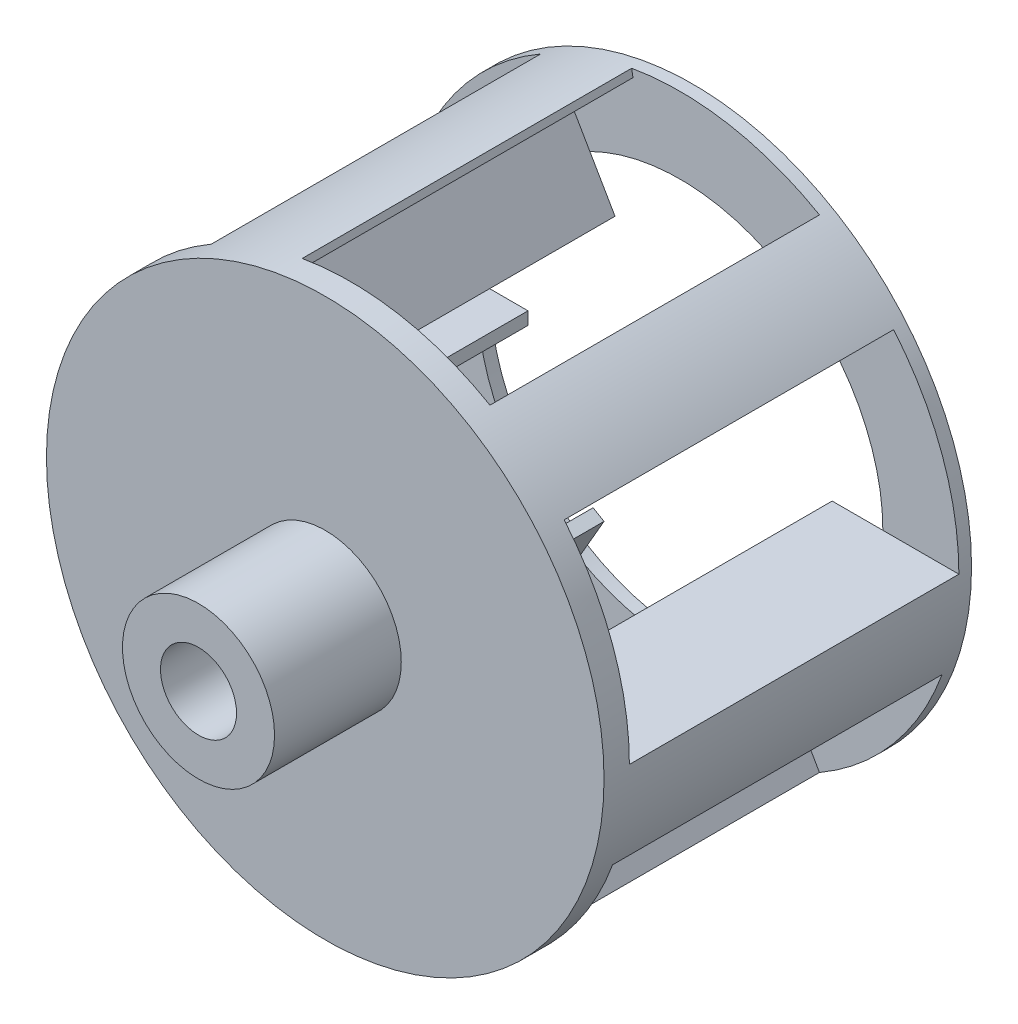
SolidWorks part; units mm, degrees
ref_plane "Front Plane" through (0, 0, 0) normal (0, 0, 1) x (1, 0, 0)
ref_plane "Top Plane" through (0, 0, 0) normal (0, 1, 0) x (1, 0, 0)
ref_plane "Right Plane" through (0, 0, 0) normal (1, 0, 0) x (0, 0, -1)
sketch "Sketch1" plane through (0, 0, 0) normal (0, 0, 1) x (1, 0, 0)
  circle A0 centre (0, 0) radius 139.7
  circle A1 centre (0, 0) radius 101.6
  circle A2 centre (0, 0) radius 38.1
  circle A3 centre (0, 0) radius 19.05
  dimension "D1" = 279.4
  dimension "D2" = 203.2
  dimension "D3" = 76.2
  dimension "D4" = 38.1
extrude "Boss-Extrude1" add sketch "Sketch1" along normal blind 63.5 contours A2 A3 region at (-37.0224, 0, 0)
extrude "Boss-Extrude2" add sketch "Sketch1<3>" against normal blind 12.7 contours A1 A2 | A0 A1 | A2 A3 region at (-135.7487, 0, 0) region at (-98.7263, 0, 0) region at (-37.0224, 0, 0)
sketch "Sketch1<3>" plane through (0, 0, 0) normal (0, 0, 1) x (1, 0, 0) same geometry as "Sketch1"
sketch "Sketch2" plane through (0, 0, -12.7) normal (0, 0, -1) x (-1, 0, 0)
  line L0 (0, 0) -> (0, 139.7) construction
  line L1 (0, 0) -> (-24.2587, 137.5776)
  line L2 (0, 0) -> (-69.85, 120.9837)
  line L3 (0, 0) -> (-139.7, 0) construction
  line L4 (5.4993, 3.175) -> (-64.3507, 124.1587)
  line L5 (-43.5993, 62.8161) -> (-32.6007, 69.1661)
  line L6 (-5.4993, -3.175) -> (-75.3493, 117.8087)
  line L7 (0, 0) -> (-107.0164, 89.7974)
  circle A0 centre (0, 0) radius 139.7 construction
  circle A1 centre (0, 0) radius 139.7
  circle A2 centre (0, 0) radius 135.89
  point P17 (-38.1, 65.9911)
  circle M7 centre (0, 0) radius 139.7
  dimension "D1" = 60
  dimension "D2" = 20
  dimension "D5" = 63.5
  dimension "D3" = 6.35
  dimension "D4" = 3.81
extrude "Boss-Extrude3" add sketch "Sketch2" along normal blind 165.1 contours A2 L6 L7 M7 | A2 L2 L6 M7 | L2 A2 L6 L5 region at (55.7586, 90.2294, -12.7) region at (71.6232, 117.7039, -12.7) region at (90.6411, 103.1, -12.7)
pattern_circular "CirPattern2" count 6 over 360 about axis through (0, 0, -12.7) along (0, 0, 1) of "Boss-Extrude3"
sketch "Sketch3" plane through (0, 0, -177.8) normal (0, 0, -1) x (-1, 0, 0)
  arc A0 (-107.0164, 89.7974) -> (-139.7, 0) centre (0, 0) ccw construction
  circle A1 centre (0, 0) radius 139.7
  circle A2 centre (0, 0) radius 101.6
  dimension "D1" = 203.2
extrude "Boss-Extrude4" add sketch "Sketch3" along normal blind 6.35
